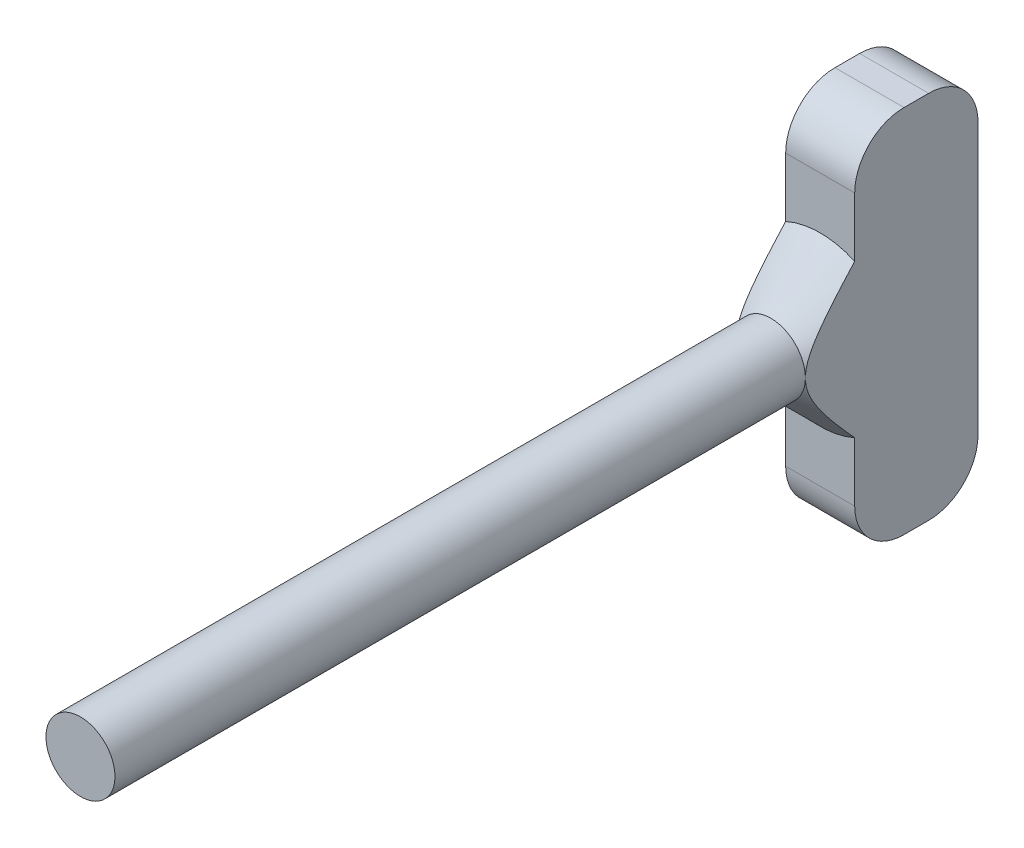
SolidWorks part; units mm, degrees
material "ABS PC"
ref_plane "Front Plane" through (0, 0, 0) normal (0, 0, 1) x (1, 0, 0)
ref_plane "Top Plane" through (0, 0, 0) normal (0, 1, 0) x (1, 0, 0)
ref_plane "Right Plane" through (0, 0, 0) normal (1, 0, 0) x (0, 0, -1)
sketch "Sketch1" plane through (0, 0, 0) normal (0, 0, 1) x (1, 0, 0)
  circle A0 centre (0, 0) radius 1.778
  dimension "D1" = 3.556
extrude "Boss-Extrude1" add sketch "Sketch1" along normal blind 38.1
sketch "Sketch2" plane through (0, 0, 0) normal (0, 0, -1) x (-1, 0, 0)
  line L1 (-1.778, -9.525) -> (1.778, -9.525)
  line L2 (-1.778, -9.525) -> (-1.778, 9.525)
  line L3 (-1.778, 9.525) -> (1.778, 9.525)
  line L4 (1.778, -9.525) -> (1.778, 9.525)
  line L5 (-1.778, -9.525) -> (1.778, 9.525) construction
  line L6 (-1.778, 9.525) -> (1.778, -9.525) construction
  circle A0 centre (0, 0) radius 1.778 construction
  point P0 (0, 0)
  dimension "D1" = 19.05
extrude "Boss-Extrude2" add sketch "Sketch2" along normal blind 6.35
fillet "Fillet2" radius 2.54 4 edges at (0, -9.525, -6.35) (0, -9.525, 0) (0, 9.525, -6.35) (0, 9.525, 0)
chamfer "Chamfer2" distance 2.54 angle 45 2 edges at (0, 1.778, 0) (0, -1.778, 0)
sketch "Sketch3" plane through (-1.778, 0, 0) normal (-1, 0, 0) x (0, 0, 1)
  line L0 (-1.905, 9.4443) -> (-1.905, -9.4443) construction
  line L1 (-6.35, -6.985) -> (-6.35, 6.985) construction
  arc A0 (0, 6.985) -> (-2.54, 9.525) centre (-2.54, 6.985) ccw construction
  arc A1 (-2.54, -9.525) -> (0, -6.985) centre (-2.54, -6.985) ccw construction
  text T0 "PGDLMFU" font "Century Gothic" height in points 9
  dimension "D1" = 4.445
extrude "Boss-Extrude3" add sketch "Sketch3" along normal blind 0.254
